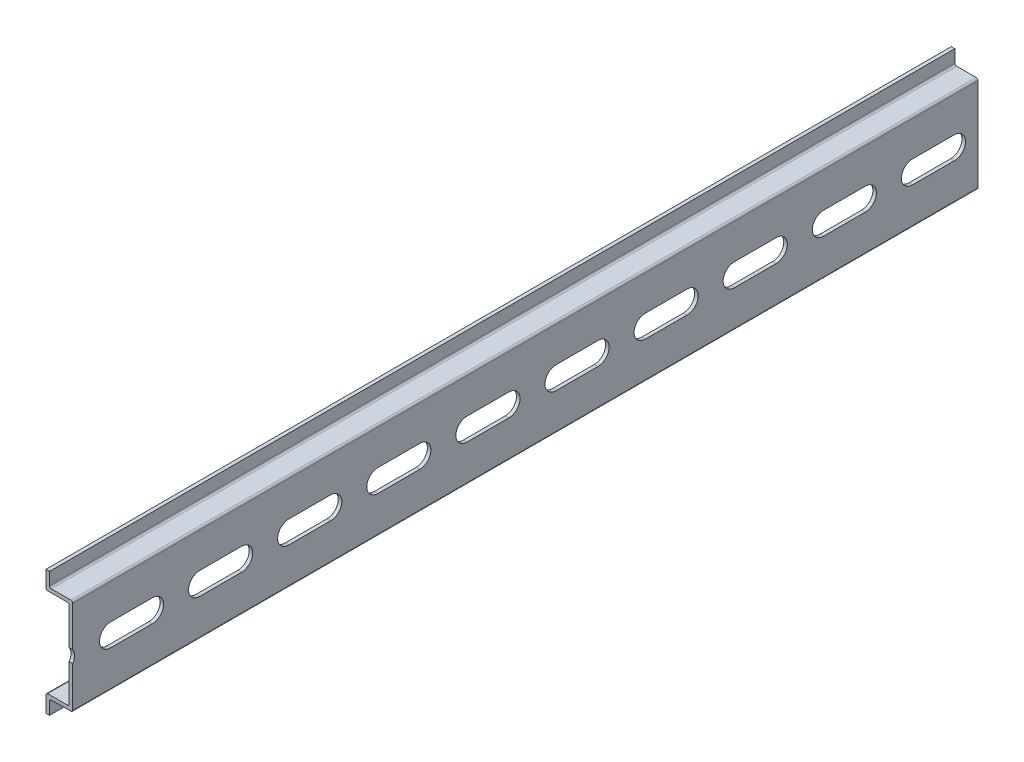
SolidWorks part; units mm, degrees
ref_plane "Front Plane" through (0, 0, 0) normal (0, 0, 1) x (1, 0, 0)
ref_plane "Top Plane" through (0, 0, 0) normal (0, 1, 0) x (1, 0, 0)
ref_plane "Right Plane" through (0, 0, 0) normal (1, 0, 0) x (0, 0, -1)
sketch "profile" plane through (0, 0, 0) normal (0, 0, 1) x (1, 0, 0)
  line L0 (0, -13.5) -> (0, 13.5) construction
  line L1 (0, 13.5) -> (-6.5, 13.5) construction
  line L2 (-6.5, 13.5) -> (-6.5, 17.5) construction
  line L3 (0, -13.5) -> (-6.5, -13.5) construction
  line L4 (-6.5, -13.5) -> (-6.5, -17.5) construction
  dimension "D1" = 27
  dimension "D2" = 35
  dimension "D3" = 6.5
sketch "Sketch3" plane through (0, 0, 0) normal (0, 0, 1) x (1, 0, 0)
  line L0 (-6.5, -13.5) -> (-6.5, -17.5) construction
  line L1 (0, -13.5) -> (-6.5, -13.5) construction
  line L2 (0, -13.5) -> (0, 13.5) construction
  line L3 (0, 13.5) -> (-6.5, 13.5) construction
  line L4 (-6.5, 13.5) -> (-6.5, 17.5) construction
  line L5 (-6.5, -13.5) -> (-6.5, -17.5)
  line L6 (0, -13.5) -> (-6.5, -13.5)
  line L7 (0, -13.5) -> (0, 13.5)
  line L8 (0, 13.5) -> (-6.5, 13.5)
  line L9 (-6.5, 13.5) -> (-6.5, 17.5)
extrude "Extrude-Thin1" add sketch "Sketch3" along normal blind 449.2625 thin thin type one direction reverse wall 1
sketch "Sketch4" plane through (0, 0, 0) normal (1, 0, 0) x (0, 0, -1)
  line L0 (0, 0) -> (-62.1077, 0) construction
  line L1 (-6.65, 0) -> (-18.35, 0) construction
  line L2 (-6.65, -3.15) -> (-18.35, -3.15)
  line L3 (-6.65, 3.15) -> (-18.35, 3.15)
  arc A0 (-6.65, -3.15) -> (-6.65, 3.15) centre (-6.65, 0) ccw
  arc A1 (-18.35, 3.15) -> (-18.35, -3.15) centre (-18.35, 0) ccw
  point P5 (-12.5, 0)
  point P10 (-3.5, 0)
  point P11 (-21.5, 0)
  point P12 (-37.5, 0)
  dimension "D1" = 18
  dimension "D2" = 6.3
  dimension "D3" = 12.5
  dimension "D4" = 25
extrude "Cut-Extrude1" cut sketch "Sketch4" against normal through all both and the other way through all
pattern_linear "LPattern1" count 18 spacing 25 along (0, 0, 1) of "Cut-Extrude1"
fillet "Fillet1" radius 0.5 8 edges at (0, -13.5, 224.6312) (0, 13.5, 224.6312) (-6.5, 13.5, 224.6312) (-6.5, -13.5, 224.6312) (-1, 12.5, 224.6312) (-1, -12.5, 224.6312) (-7.5, -12.5, 224.6312) (-7.5, 12.5, 224.6312)
ref_plane "Contact Plane 1" through (-1, 0, 0) normal (-1, 0, 0) x (0, 0, 1)
sketch "Sketch5" plane through (0, 0, 449.2625) normal (0, 0, 1) x (1, 0, 0)
  line L1 (-11.0924, 21.6059) -> (2.0658, 21.6059)
  line L2 (-11.0924, 21.6059) -> (-11.0924, -18.4363)
  line L3 (-11.0924, -18.4363) -> (2.0658, -18.4363)
  line L4 (2.0658, 21.6059) -> (2.0658, -18.4363)
extrude "Cut-Extrude2" cut sketch "Sketch5" against normal blind 195.2625
equation "\"D3@LPattern1\"=\"D4@Sketch4\""
equation "\"D1@LPattern1\" = \"Length@Extrude-Thin1\" / \"D3@LPattern1\""
